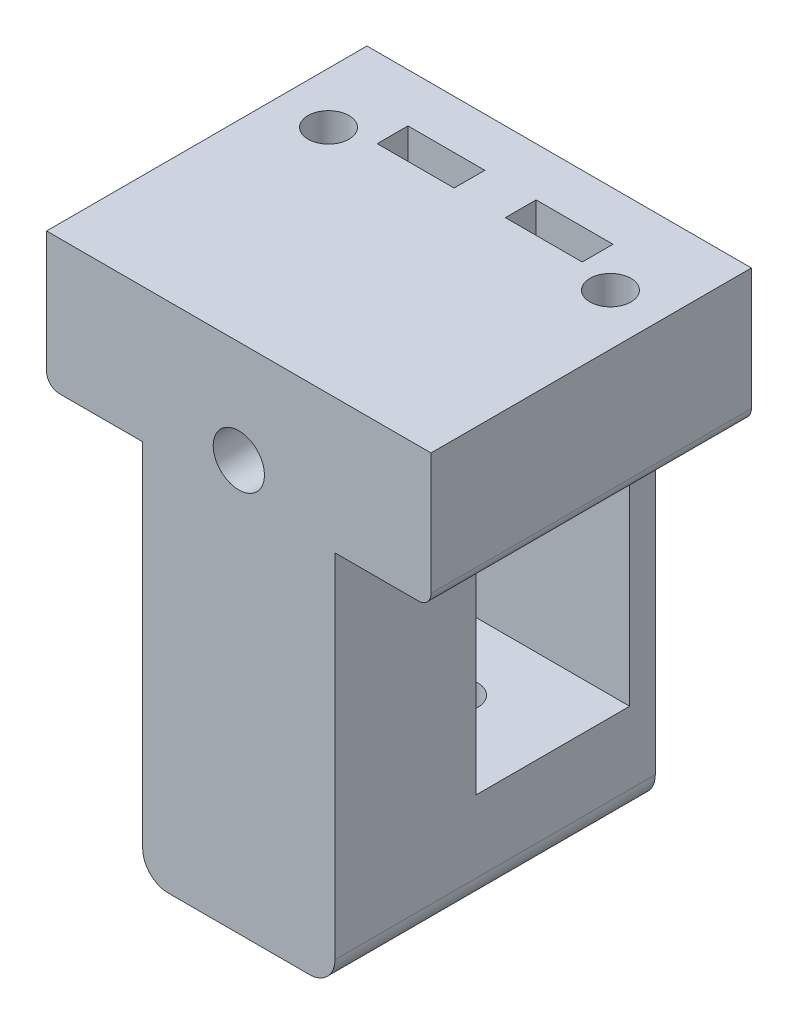
SolidWorks part; units mm, degrees
ref_plane "Front Plane" through (0, 0, 0) normal (0, 0, 1) x (1, 0, 0)
ref_plane "Top Plane" through (0, 0, 0) normal (0, 1, 0) x (1, 0, 0)
ref_plane "Right Plane" through (0, 0, 0) normal (1, 0, 0) x (0, 0, -1)
sketch "Sketch1" plane through (0, 0, 0) normal (0, 0, 1) x (1, 0, 0)
  line L0 (0, 40) -> (0, 50.5)
  line L3 (0, 50.5) -> (30, 50.5)
  line L7 (0, 40) -> (7.5, 40)
  line L8 (7.5, 10.5) -> (7.5, 40)
  line L11 (30, 40) -> (22.5, 40)
  line L12 (22.5, 10.5) -> (22.5, 40)
  line L13 (30, 40) -> (30, 50.5)
  line L14 (7.5, 10.5) -> (22.5, 10.5)
extrude "Boss-Extrude1" add sketch "Sketch1" along normal blind 25
sketch "Sketch2" plane through (7.5, 0, 0) normal (-1, 0, 0) x (0, 0, 1)
  line L1 (2, 18.13) -> (14, 18.13)
  line L2 (2, 18.13) -> (2, 34.13)
  line L3 (2, 34.13) -> (14, 34.13)
  line L4 (14, 18.13) -> (14, 34.13)
extrude "Cut-Extrude1" cut sketch "Sketch2" against normal through all
sketch "Sketch3" plane through (0, 50.5, 0) normal (0, 1, 0) x (1, 0, 0)
  circle A0 centre (4, -7) radius 1.6
  circle A1 centre (26, -7) radius 1.6
extrude "Cut-Extrude2" cut sketch "Sketch3" against normal through all
sketch "Sketch4" plane through (0, 10.5, 0) normal (0, -1, 0) x (1, 0, 0)
  circle A0 centre (15, 8) radius 1.65
extrude "Cut-Extrude3" cut sketch "Sketch4" against normal up to surface (7.63 mm away) up to face at (15, 18.13, 8)
ref_plane "Plane1" through (0, 0, 15) normal (0, 0, 1) x (1, 0, 0)
sketch "Sketch6" plane through (0, 0, 15) normal (0, 0, 1) x (1, 0, 0)
  circle A0 centre (15, 42.5) radius 2
extrude "Cut-Extrude4" cut sketch "Sketch6" along normal up to surface (10 mm away) up to face at (15, 35.25, 25)
sketch "Sketch7" plane through (0, 0, 0) normal (0, 0, -1) x (-1, 0, 0)
  circle A0 centre (-10, 42.5) radius 1.6
  circle A1 centre (-20, 42.5) radius 1.6
sketch "Sketch8" plane through (0, 0, 0) normal (0, 0, -1) x (-1, 0, 0)
  line L0 (-18.3, 42.5) -> (-11.7, 42.5) construction
  line L1 (-18.3, 45.05) -> (-11.7, 45.05) construction
  line L2 (-18.3, 39.95) -> (-11.7, 39.95) construction
  arc A1 (-18.3, 45.05) -> (-18.3, 39.95) centre (-18.3, 42.5) ccw construction
  arc A2 (-11.7, 39.95) -> (-11.7, 45.05) centre (-11.7, 42.5) ccw construction
  circle A3 centre (-15, 42.5) radius 2.65
  point P3 (-15, 42.5)
extrude "Cut-Extrude6" cut sketch "Sketch8" against normal blind 3
sketch "Sketch9" plane through (0, 34.13, 0) normal (0, -1, 0) x (1, 0, 0)
  circle A0 centre (15, 8) radius 2.45
ref_axis "Axis1" through (15, 34.13, 8) along (0, -1, 0)
ref_plane "Plane2" through (15, 0, 0) normal (-1, 0, 0) x (0, 0, 1)
sketch "Sketch11" plane through (15, 0, 0) normal (-1, 0, 0) x (0, 0, 1)
  line L0 (10.45, 34.13) -> (8, 34.13)
  line L1 (14, 34.13) -> (2, 34.13) construction
  line L2 (5.55, 34.13) -> (10.45, 34.13) construction
  line L3 (8, 34.13) -> (8, 37.36)
  line L4 (8, 37.36) -> (11.15, 37.36)
  line L5 (11.15, 37.36) -> (11.15, 35.66)
  line L6 (10.45, 34.13) -> (10.45, 35.66)
  line L7 (10.45, 35.66) -> (11.15, 35.66)
revolve "Cut-Revolve1" cut sketch "Sketch11" angle 360 about axis through (15, 34.13, 8) along (0, -1, 0)
sketch "Sketch15" plane through (0, 0, 3) normal (0, 0, -1) x (-1, 0, 0)
  circle A1 centre (-15, 42.5) radius 1
ref_plane "Plane3" through (0, 42.5, 0) normal (0, -1, 0) x (-1, 0, 0)
sketch "Sketch16" plane through (0, 42.5, 0) normal (0, -1, 0) x (-1, 0, 0)
  line L0 (-16, -3) -> (-16, -11.0289)
  line L2 (-16.1119, -11.8407) -> (-17, -15)
  line L5 (-17, -15) -> (-15, -15)
  line L7 (-15, -15) -> (-15, -3)
  line L8 (-15, -3) -> (-16, -3)
  arc A0 (-16.1119, -11.8407) -> (-16, -11.0289) centre (-19, -11.0289) ccw
  dimension "D1" = 3
sketch "Sketch17" plane through (0, 42.5, 0) normal (0, -1, 0) x (-1, 0, 0)
  circle A0 centre (-15, -8) radius 1
loft "Cut-Loft5" cut profiles "Sketch9", "Sketch17" connector at (14.9026, 34.13, 10.4481) connector at (14.9653, 42.5, 8.9994)
ref_axis "Axis2" through (15, 42.5, 25) along (0, 0, -1)
revolve "Cut-Revolve2" cut sketch "Sketch16" angle 360 about axis through (15, 42.5, 25) along (0, 0, -1)
fillet "Fillet4" radius 1 1 edges at (30, 40, 12.5) type face fillet first side face at (30, 45.25, 12.5) second side face at (24.4, 40, 7)
fillet "Fillet5" radius 1 1 edges at (0, 40, 12.5) type face fillet first side face at (0, 45.25, 12.5) second side face at (4, 40, 8.6)
fillet "Fillet6" radius 2 1 edges at (22.5, 10.5, 12.5) type face fillet first side face at (15, 10.5, 6.35) second side face at (22.5, 26.13, 8)
fillet "Fillet7" radius 2 1 edges at (7.5, 10.5, 12.5) type face fillet first side face at (15, 10.5, 6.35) second side face at (7.5, 26.13, 8)
sketch "Sketch18" plane through (0, 50.5, 0) normal (0, 1, 0) x (1, 0, 0)
  line L8 (7, -3.8) -> (13, -3.8)
  line L9 (7, -3.8) -> (7, -6.2)
  line L10 (7, -6.2) -> (13, -6.2)
  line L11 (13, -3.8) -> (13, -6.2)
  line L12 (7, -3.8) -> (13, -6.2) construction
  line L13 (7, -6.2) -> (13, -3.8) construction
  line L14 (17, -3.8) -> (23, -3.8)
  line L15 (17, -3.8) -> (17, -6.2)
  line L16 (17, -6.2) -> (23, -6.2)
  line L17 (23, -3.8) -> (23, -6.2)
  line L18 (17, -3.8) -> (23, -6.2) construction
  line L19 (17, -6.2) -> (23, -3.8) construction
  point P9 (20, -5)
  point P10 (10, -5)
extrude "Cut-Extrude7" cut sketch "Sketch18" against normal blind 10.8
extrude "Cut-Extrude11" cut sketch "Sketch7" against normal blind 8 contours A0
extrude "Cut-Extrude12" cut sketch "Sketch7<3>" against normal blind 8 contours A1
sketch "Sketch7<3>" plane through (0, 0, 0) normal (0, 0, -1) x (-1, 0, 0) same geometry as "Sketch7"
